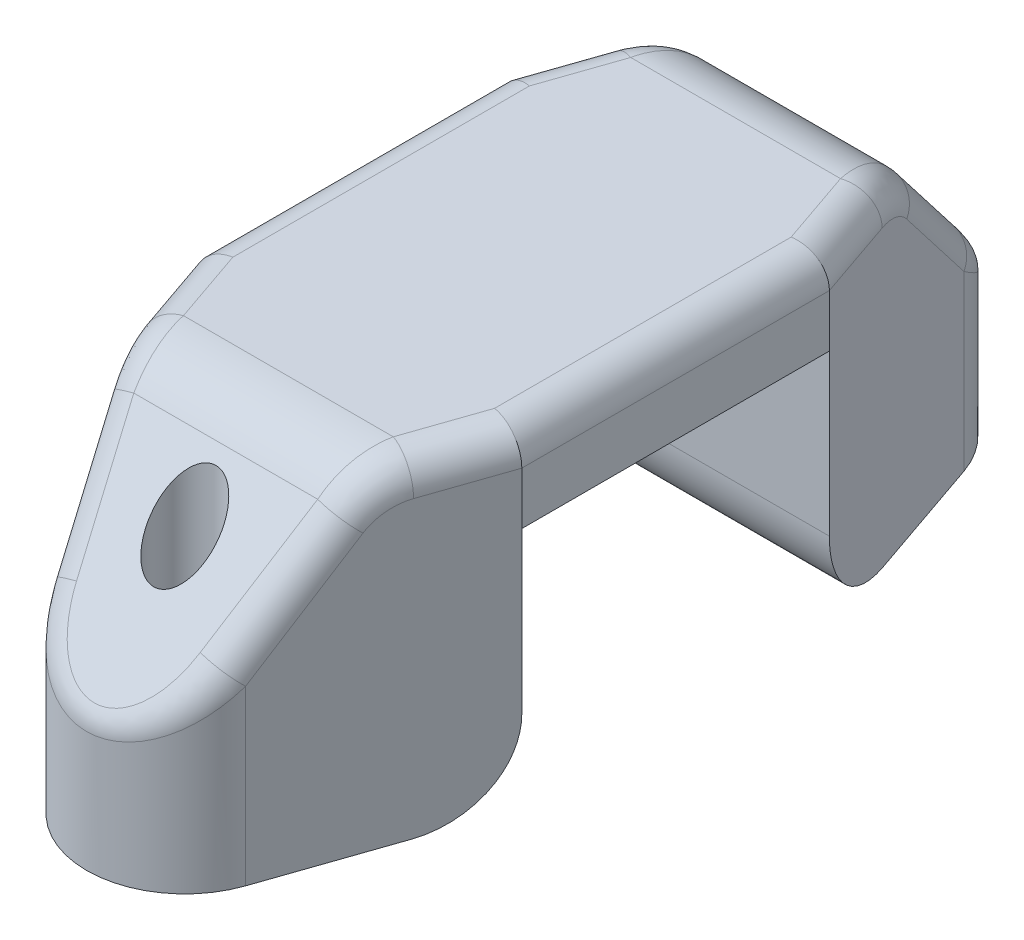
SolidWorks part; units mm, degrees
ref_plane "Front Plane" through (0, 0, 0) normal (0, 0, 1) x (1, 0, 0)
ref_plane "Top Plane" through (0, 0, 0) normal (0, 1, 0) x (1, 0, 0)
ref_plane "Right Plane" through (0, 0, 0) normal (1, 0, 0) x (0, 0, -1)
sketch "Sketch1" plane through (0, 0, 0) normal (0, 1, 0) x (1, 0, 0)
  line L0 (0, 0) -> (12.9383, 0) construction
  line L1 (-6.35, -5.969) -> (6.35, -5.969)
  line L2 (-6.35, -5.969) -> (-6.35, 5.969)
  line L3 (-6.35, 5.969) -> (6.35, 5.969)
  line L4 (6.35, -5.969) -> (6.35, 5.969)
  line L5 (-6.35, -5.969) -> (6.35, 5.969) construction
  line L6 (-6.35, 5.969) -> (6.35, -5.969) construction
  line L7 (-6.35, -5.969) -> (-3.602, -13.9415)
  line L8 (6.35, -5.969) -> (3.602, -13.9415)
  line L9 (-6.35, 5.969) -> (-3.602, 13.9415)
  line L10 (6.35, 5.969) -> (3.602, 13.9415)
  circle A0 centre (0, -12.7) radius 1.2065
  circle A1 centre (0, 12.7) radius 1.2065
  circle A2 centre (0, -12.7) radius 3.81
  circle A4 centre (0, 12.7) radius 3.81
  point P0 (0, 0)
  dimension "D3" = 2.413
  dimension "D4" = 25.4
  dimension "D5" = 7.62
  dimension "D1" = 11.938
  dimension "D2" = 12.7
extrude "Boss-Extrude1" add sketch "Sketch1" along normal blind 12.7 contours A4 A1 | L10 A4 L9 L3 | L1 L4 L3 L2 | A2 L8 L1 L7 | A2 A0 region at (0, 0, 0) region at (0, 0, 8.1344) region at (0, 0, -8.1344) region at (-0.6116, 0, 9.0486) region at (0, 0, -16.4022)
sketch "Sketch2" plane through (6.35, 0, 0) normal (1, 0, 0) x (0, 0, -1)
  line L0 (5.969, 12.7) -> (5.969, 0) construction
  line L1 (-5.969, 9.398) -> (5.969, 9.398)
  line L2 (-5.969, 9.398) -> (-5.969, 0)
  line L3 (-5.969, 0) -> (5.969, 0)
  line L4 (5.969, 9.398) -> (5.969, 0)
  line L5 (-5.969, 9.398) -> (5.969, 0) construction
  line L6 (-5.969, 0) -> (5.969, 9.398) construction
  point P0 (0, 4.699)
  dimension "D1" = 9.398
extrude "Cut-Extrude1" cut sketch "Sketch2" against normal through all
sketch "Sketch3" plane through (6.35, 0, 0) normal (1, 0, 0) x (0, 0, -1)
  line L0 (-16.51, 5.1324) -> (-16.51, 12.7)
  line L1 (-16.51, 12.7) -> (-16.51, 0) construction
  line L2 (-16.51, 12.7) -> (-10.16, 12.7)
  line L3 (-5.969, 12.7) -> (-13.9415, 12.7) construction
  line L4 (-10.16, 12.7) -> (-16.51, 5.1324)
  line L5 (0, 0) -> (0, 16.4183) construction
  line L6 (10.16, 12.7) -> (16.51, 5.1324)
  line L7 (16.51, 12.7) -> (10.16, 12.7)
  line L8 (16.51, 5.1324) -> (16.51, 12.7)
  dimension "D1" = 50
  dimension "D2" = 6.35
extrude "Cut-Extrude2" cut sketch "Sketch3" against normal through all
fillet "Fillet1" radius 3.175 4 edges at (0, 0, -5.969) (0, 0, 5.969) (0, 12.7, -10.16) (0, 12.7, 10.16)
fillet "Fillet2" radius 1.27 16 edges at (-5.8829, 12.7, -7.3242) (5.8829, 12.7, -7.3242) (4.0897, 9.8796, -12.5266) (0, 5.1324, -16.51) (-4.0897, 9.8796, -12.5266) (5.8829, 12.7, 7.3242) (-5.8829, 12.7, 7.3242) (-4.9533, 12.4025, 10.0213) (-4.0897, 9.8796, 12.5266) (0, 5.1324, 16.51) (4.0897, 9.8796, 12.5266) (4.9533, 12.4025, -10.0213) (-4.9533, 12.4025, -10.0213) (-6.35, 12.7, 0) (6.35, 12.7, 0) (4.9533, 12.4025, 10.0213)
